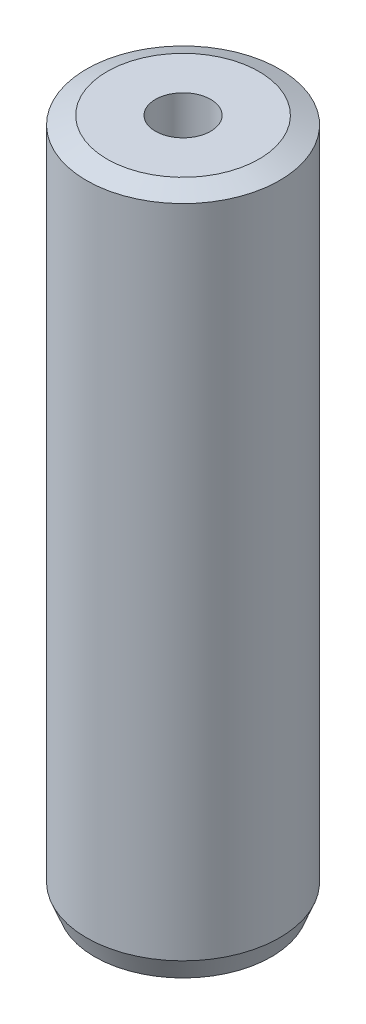
SolidWorks part; units mm, degrees
ref_plane "Front Plane" through (0, 0, 0) normal (0, 0, 1) x (1, 0, 0)
ref_plane "Top Plane" through (0, 0, 0) normal (0, 1, 0) x (1, 0, 0)
ref_plane "Right Plane" through (0, 0, 0) normal (1, 0, 0) x (0, 0, -1)
sketch "Sketch1" plane through (0, 0, 0) normal (0, 1, 0) x (1, 0, 0)
  circle A0 centre (0, 0) radius 22.5
  dimension "SHAFT_OD" = 45
extrude "Boss-Extrude1" add sketch "Sketch1" along normal blind 159.5267
sketch "Sketch2" plane through (0, 0, 0) normal (0, 1, 0) x (1, 0, 0)
  circle A0 centre (0, 0) radius 6.4411
  dimension "BORE_D" = 12.8821
extrude "Cut-Extrude1" cut sketch "Sketch2" along normal through all
chamfer "Chamfer1" distance 1.907 angle 68.344 2 edges at (0, 159.5267, 22.5) (0, 0, 22.5) first distance on face at (0, 159.5267, 22.5) first distance on face at (0, 0, 6.4411)
